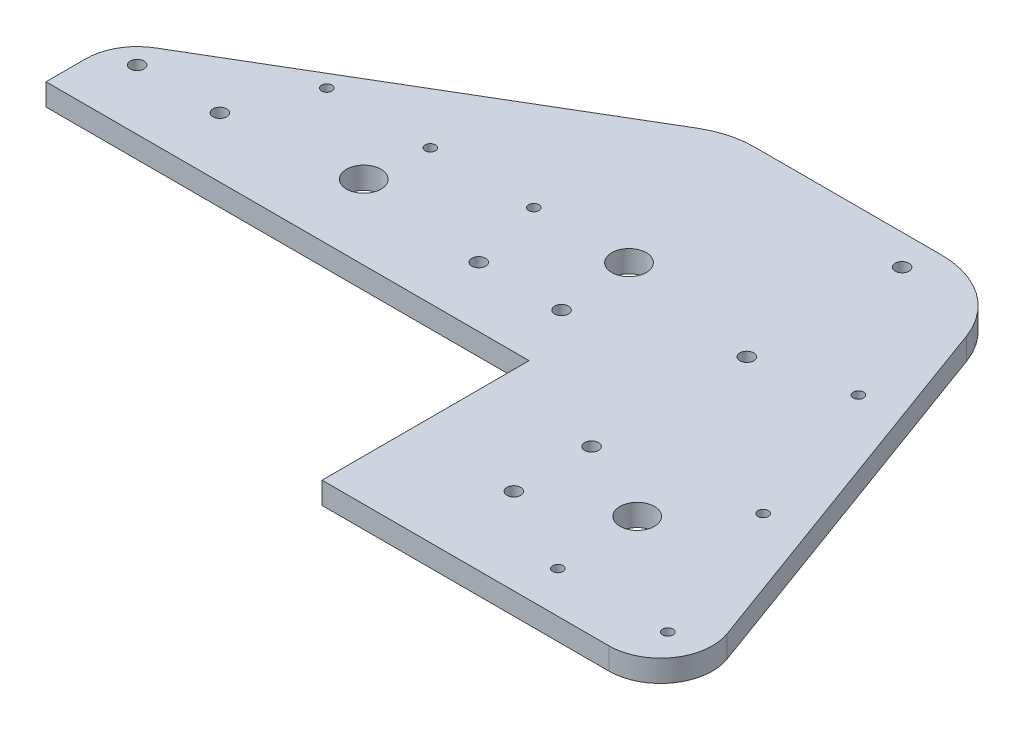
SolidWorks part; units mm, degrees
material "6063-T5"
ref_plane "Front" through (0, 0, 0) normal (0, 0, 1) x (1, 0, 0)
ref_plane "Top" through (0, 0, 0) normal (0, 1, 0) x (1, 0, 0)
ref_plane "Right" through (0, 0, 0) normal (1, 0, 0) x (0, 0, -1)
sketch "Sketch1" plane through (0, 0, 0) normal (0, 1, 0) x (1, 0, 0)
  line L0 (145, 175) -> (180.6, 175)
  line L1 (0, 0) -> (145, 0)
  line L2 (0, 0) -> (0, 175)
  line L3 (0, 175) -> (145, 175)
  line L4 (145, 0) -> (145, 175)
  line L5 (180.6, 175) -> (180.6, 0)
  line L6 (180.6, 0) -> (145, 0)
  line L7 (145, 0) -> (145, 60)
  line L8 (145, 60) -> (140, 60)
  line L9 (140, 60) -> (140, 0)
  line L10 (140, 60) -> (0, 60)
  line L11 (180.6, 175) -> (160.6, 175)
  line L12 (0, 60) -> (0, 80)
  line L13 (160.6, 175) -> (0, 80)
  line L14 (0, 60) -> (70.5, 60)
  line L15 (70.5, 60) -> (70.5, 81.59)
  line L16 (70.5, 81.59) -> (129.875, 81.59)
  line L17 (180.6, 0) -> (244.6, 0)
  line L18 (244.6, 0) -> (180.6, 175)
  line L19 (129.875, 81.59) -> (129.875, 99.09)
  line L20 (244.6, 0) -> (194.75, 0)
  line L21 (194.75, 0) -> (194.75, 36.59)
  circle A0 centre (70.5, 81.59) radius 5
  circle A2 centre (129.875, 99.09) radius 5
  circle A3 centre (194.75, 36.59) radius 5
  dimension "D10" = 59.375
  dimension "D11" = 64
  dimension "D13" = 36.59
  dimension "D1" = 175
  dimension "D2" = 145
  dimension "D3" = 35.6
  dimension "D4" = 60
  dimension "D5" = 5
  dimension "D6" = 20
  dimension "D7" = 20
  dimension "D8" = 70.5
  dimension "D9" = 21.59
  dimension "D12" = 17.5
  dimension "D14" = 49.85
extrude "Boss-Extrude2" add sketch "Sketch1" along normal blind 6.35 contours A2 A0 L10 L8 L4 L13 L2 | L0 L13 L4 L6 L5 | L17 L18 L5 | L8 L9 L1 L4 region at (162.9473, 0, -86.5132) region at (88.7844, 0, -96.4223) region at (202.0355, 0, -58.6426) region at (142.5, 0, -30)
sketch "Sketch3" plane through (0, 6.35, 0) normal (0, 1, 0) x (1, 0, 0)
  line L0 (0, 60) -> (0, 99.0944)
  line L1 (0, 99.0944) -> (42.2796, 99.0944)
  line L2 (42.2796, 99.0944) -> (32.2796, 99.0944)
  line L3 (160.6, 175) -> (0, 80) construction
  line L4 (42.2796, 99.0944) -> (72.2796, 99.0944)
  line L5 (72.2796, 99.0944) -> (102.2796, 99.0944)
  line L6 (102.2796, 99.0944) -> (208.3598, 99.0944)
  line L7 (244.6, 0) -> (180.6, 175) construction
  line L8 (208.3598, 99.0944) -> (196.3598, 99.0944)
  line L9 (244.6, 0) -> (232.0087, 0)
  line L10 (244.6, 0) -> (140, 0) construction
  line L11 (240.2114, 12) -> (228.2114, 12)
  line L12 (228.2114, 12) -> (232.0087, 12)
  line L13 (232.0087, 12) -> (232.0087, 0)
  line L14 (196.3598, 99.0944) -> (228.2114, 12)
  line L15 (228.2114, 12) -> (212.2856, 55.5472)
  line L16 (212.2856, 55.5472) -> (196.3598, 99.0944)
  line L17 (228.2114, 12) -> (196.3598, 12)
  circle A0 centre (42.2796, 99.0944) radius 1.5
  circle A1 centre (72.2796, 99.0944) radius 1.5
  circle A2 centre (102.2796, 99.0944) radius 1.5
  circle A3 centre (196.3598, 99.0944) radius 1.5
  circle A4 centre (212.2856, 55.5472) radius 1.5
  circle A5 centre (228.2114, 12) radius 1.5
  circle A6 centre (196.3598, 12) radius 1.5
  dimension "D5" = 12
  dimension "D6" = 12
  dimension "D1" = 39.0944
  dimension "D2" = 10
  dimension "D3" = 30
  dimension "D4" = 30
  dimension "D7" = 12
extrude "Cut-Extrude1" cut sketch "Sketch3" against normal blind 6.35 contours L2 A0 L4 | L4 A0 L2 | L5 A1 L4 | L4 A1 L5 | A2 | L5 A2 L6 | L6 A3 | L6 A3 | L14 A3 L6 | L14 A4 | L14 A4 | L12 A5 L14 | L14 A5 L17 | L17 A5 L12 | A6 region at (42.2796, 6.35, -99.731) region at (228.7002, 6.35, -12.6992) region at (227.4417, 6.35, -12.5381) region at (212.8835, 6.35, -55.7659) region at (211.6877, 6.35, -55.3285) region at (196.3598, 6.35, -99.731) region at (195.871, 6.35, -98.3952) region at (102.2796, 6.35, -99.731) region at (102.2796, 6.35, -98.4578) region at (72.2796, 6.35, -99.731) region at (72.2796, 6.35, -98.4578) region at (42.2796, 6.35, -98.4578) region at (197.1294, 6.35, -98.5563) region at (228.2114, 6.35, -11.3634)
sketch "Sketch4" plane through (0, 6.35, 0) normal (0, 1, 0) x (1, 0, 0)
  line L0 (170.6, 175) -> (170.6, 137.5)
  line L1 (160.6, 175) -> (180.6, 175) construction
  line L2 (170.6, 137.5) -> (170.6, 92.5)
  line L3 (170.6, 92.5) -> (170.6, 47.5)
  line L4 (170.6, 160) -> (170.6, 25)
  circle A0 centre (170.6, 137.5) radius 2
  circle A1 centre (170.6, 92.5) radius 2
  circle A2 centre (170.6, 47.5) radius 2
  circle A3 centre (170.6, 160) radius 2
  circle A4 centre (170.6, 25) radius 2
  dimension "D4" = 15
  dimension "D1" = 37.5
  dimension "D2" = 45
  dimension "D3" = 45
  dimension "D5" = 135
extrude "Cut-Extrude2" cut sketch "Sketch4" against normal blind 10 contours L0 A3 | L0 A3 | A0 | A1 | A2 | A4 region at (171.4488, 6.35, -160) region at (169.7512, 6.35, -160)
sketch "Sketch6" plane through (0, 0, 0) normal (0, -1, 0) x (-1, 0, 0)
  line L0 (-33, 77.4) -> (-9, 77.4)
  circle A0 centre (-132, 77.4) radius 2
  circle A1 centre (-108, 77.4) radius 2
  circle A2 centre (-33, 77.4) radius 2
  circle A3 centre (-33, 77.4) radius 2
  circle A4 centre (-9, 77.4) radius 2
  dimension "D1" = 24
extrude "Cut-Extrude3" cut sketch "Sketch6" against normal blind 6.35 contours A2 | A4 | A1 | A0
sketch "Sketch7" plane through (0, 6.35, 0) normal (0, 1, 0) x (1, 0, 0)
  line L7 (170.6, 25) -> (194.75, 36.59)
  line L8 (194.75, 36.59) -> (196.3598, 12)
  line L9 (194.75, 36.59) -> (170.6, 47.5)
  line L10 (170.6, 47.5) -> (212.2856, 55.5472)
  line L11 (212.2856, 55.5472) -> (194.75, 36.59)
  line L12 (170.6, 47.5) -> (170.6, 92.5)
  line L13 (170.6, 92.5) -> (170.6, 137.5)
  line L14 (10, 74.2968) -> (10, 70)
  line L15 (10, 70) -> (150, 70)
  line L16 (150, 70) -> (150, 10)
  line L17 (150, 10) -> (230.2951, 10)
  line L18 (230.2951, 10) -> (173.6094, 165)
  line L19 (173.6094, 165) -> (163.3362, 165)
  line L20 (163.3362, 165) -> (10, 74.2968)
  line L21 (10, 74.2968) -> (10, 70)
  line L22 (10, 70) -> (150, 70)
  line L23 (150, 70) -> (150, 10)
  line L24 (150, 10) -> (230.2951, 10)
  line L25 (230.2951, 10) -> (173.6094, 165)
  line L26 (173.6094, 165) -> (163.3362, 165)
  line L27 (163.3362, 165) -> (10, 74.2968)
  line L28 (170.6, 137.5) -> (170.6, 160)
  line L29 (170.6, 92.5) -> (196.3598, 99.0944)
  line L30 (170.6, 92.5) -> (129.875, 99.09)
  line L31 (129.875, 99.09) -> (132, 77.4)
  line L32 (132, 77.4) -> (108, 77.4)
  line L33 (108, 77.4) -> (102.2796, 99.0944)
  line L34 (102.2796, 99.0944) -> (129.875, 99.09)
  line L35 (102.2796, 99.0944) -> (72.2796, 99.0944)
  line L36 (72.2796, 99.0944) -> (70.5, 81.59)
  line L37 (70.5, 81.59) -> (108, 77.4)
  line L38 (70.5, 81.59) -> (33, 77.4)
  line L39 (33, 77.4) -> (72.2796, 99.0944)
  line L40 (129.875, 99.09) -> (109.6667, 133.2527)
  line L41 (102.2796, 99.0944) -> (89.2262, 121.1615)
  line L42 (42.2796, 99.0944) -> (72.2796, 99.0944)
  line L43 (129.875, 99.09) -> (170.6, 137.5)
  line L44 (170.6, 92.5) -> (150, 70)
  line L45 (133.3056, 95.4526) -> (174.0306, 133.8626)
  line L46 (126.4444, 102.7274) -> (167.1694, 141.1374)
  line L47 (171.3987, 97.4358) -> (130.6737, 104.0258)
  line L48 (169.8013, 87.5642) -> (129.0763, 94.1542)
  line L49 (171.84, 87.6562) -> (197.5998, 94.2506)
  line L50 (169.36, 97.3438) -> (195.1198, 103.9382)
  line L51 (175.6, 47.5) -> (175.6, 92.5)
  line L52 (175.6, 92.5) -> (175.6, 137.5)
  line L53 (165.6, 47.5) -> (165.6, 92.5)
  line L54 (165.6, 92.5) -> (165.6, 137.5)
  line L55 (112.8347, 78.6748) -> (106.9371, 101.0416)
  line L56 (106.9371, 101.0416) -> (93.5296, 123.7072)
  line L57 (103.1653, 76.1252) -> (97.6221, 97.1472)
  line L58 (97.6221, 97.1472) -> (84.9227, 118.6159)
  line L59 (70.5, 76.5589) -> (33.5552, 72.4309)
  line L60 (70.5, 76.5589) -> (107.4448, 72.4309)
  line L61 (70.5, 86.6211) -> (32.4448, 82.3691)
  line L62 (70.5, 86.6211) -> (108.5552, 82.3691)
  line L63 (134.743, 100.6812) -> (136.9762, 77.8875)
  line L64 (134.743, 100.6812) -> (113.9701, 135.7984)
  line L65 (125.007, 97.4988) -> (127.0238, 76.9125)
  line L66 (125.007, 97.4988) -> (105.3632, 130.7071)
  line L67 (170.6, 47.5) -> (170.6, 25)
  line L68 (170.6, 25) -> (170.6, 10)
  line L69 (170.6, 25) -> (196.3598, 12)
  line L70 (175.6, 47.5) -> (175.6, 25)
  line L71 (175.6, 25) -> (175.6, 10)
  line L72 (172.8527, 29.4638) -> (198.6125, 16.4638)
  line L73 (165.6, 47.5) -> (165.6, 25)
  line L74 (165.6, 25) -> (165.6, 10)
  line L75 (168.3473, 20.5362) -> (194.1071, 7.5362)
  line L76 (172.7634, 20.4922) -> (197.773, 32.4948)
  line L77 (215.9561, 52.152) -> (197.773, 32.4948)
  line L78 (168.4366, 29.5078) -> (191.727, 40.6852)
  line L79 (208.6151, 58.9424) -> (191.727, 40.6852)
  line L80 (171.5477, 42.5906) -> (213.2333, 50.6378)
  line L81 (169.6523, 52.4094) -> (211.3379, 60.4566)
  line L82 (189.7607, 36.2634) -> (191.3704, 11.6734)
  line L83 (199.7393, 36.9166) -> (201.3491, 12.3266)
  line L84 (194.75, 36.59) -> (228.2114, 12)
  line L85 (191.7891, 32.5609) -> (225.2506, 7.9709)
  line L86 (197.7109, 40.6191) -> (231.1723, 16.0291)
  line L87 (170.6, 92.5) -> (212.2856, 55.5472)
  line L88 (196.3598, 99.0944) -> (170.6, 47.5)
  line L89 (167.2833, 88.7585) -> (208.9688, 51.8057)
  line L90 (173.9167, 96.2415) -> (215.6023, 59.2887)
  line L91 (191.8863, 101.3279) -> (166.1266, 49.7335)
  line L92 (200.8332, 96.8609) -> (175.0734, 45.2665)
  line L93 (166.9122, 95.8764) -> (146.3122, 73.3764)
  line L94 (174.2878, 89.1236) -> (153.6878, 66.6236)
  line L95 (35.4173, 73.0232) -> (74.6969, 94.7176)
  line L96 (30.5827, 81.7768) -> (69.8622, 103.4712)
  line L97 (72.2796, 99.0944) -> (67.0025, 108.0155)
  line L98 (76.583, 101.64) -> (71.3059, 110.5612)
  line L99 (67.9761, 96.5488) -> (62.699, 105.4699)
  line L100 (67.3052, 99.6001) -> (65.5256, 82.0957)
  line L101 (77.2539, 98.5887) -> (75.4744, 81.0843)
  line L102 (175.6, 137.5) -> (175.6, 160)
  line L103 (165.6, 137.5) -> (165.6, 160)
  line L104 (42.2796, 99.0944) -> (70.5, 81.59)
  line L105 (39.644, 94.8454) -> (67.8645, 77.341)
  line L106 (44.9151, 103.3434) -> (73.1355, 85.839)
  line L107 (9, 77.4) -> (33, 77.4)
  line L108 (9, 72.4) -> (33, 72.4)
  line L109 (9, 82.4) -> (33, 82.4)
  line L110 (102.2796, 104.0944) -> (72.2796, 104.0944)
  line L111 (102.2796, 94.0944) -> (72.2796, 94.0944)
  line L112 (132, 82.4) -> (108, 82.4)
  line L113 (132, 72.4) -> (108, 72.4)
  line L114 (102.2788, 94.0944) -> (129.8742, 94.09)
  line L115 (102.2804, 104.0944) -> (129.8758, 104.09)
  circle A0 centre (9, 77.4) radius 8
  circle A1 centre (42.2796, 99.0944) radius 7.5
  circle A2 centre (33, 77.4) radius 7.5
  circle A3 centre (72.2796, 99.0944) radius 7.5
  circle A4 centre (70.5, 81.59) radius 12.5
  circle A5 centre (102.2796, 99.0944) radius 7.5
  circle A6 centre (108, 77.4) radius 8
  circle A7 centre (132, 77.4) radius 8
  circle A8 centre (129.875, 99.09) radius 12.5
  circle A9 centre (170.6, 160) radius 8
  circle A10 centre (170.6, 137.5) radius 8
  circle A11 centre (170.6, 92.5) radius 8
  circle A12 centre (196.3598, 99.0944) radius 7.5
  circle A13 centre (170.6, 47.5) radius 8
  circle A14 centre (194.75, 36.59) radius 12.5
  circle A15 centre (170.6, 25) radius 8
  circle A16 centre (196.3598, 12) radius 7.5
  circle A17 centre (212.2856, 55.5472) radius 7.5
  circle A18 centre (228.2114, 12) radius 7.5
  circle A19 centre (150, 70) radius 5
  dimension "D1" = 15
  dimension "D2" = 16
  dimension "D3" = 15
  dimension "D4" = 25
  dimension "D5" = 15
  dimension "D6" = 15
  dimension "D7" = 25
  dimension "D8" = 16
  dimension "D9" = 16
  dimension "D10" = 16
  dimension "D11" = 16
  dimension "D12" = 16
  dimension "D13" = 15
  dimension "D14" = 16
  dimension "D15" = 16
  dimension "D16" = 25
  dimension "D17" = 15
  dimension "D18" = 15
  dimension "D19" = 15
  dimension "D20" = 10
  dimension "D21" = 5
  dimension "D22" = 5
  dimension "D23" = 5
  dimension "D24" = 5
  dimension "D25" = 5
  dimension "D26" = 5
  dimension "D27" = 5
  dimension "D28" = 5
  dimension "D29" = 5
  dimension "D30" = 5
  dimension "D31" = 5
  dimension "D32" = 5
  dimension "D33" = 5
  dimension "D34" = 5
  dimension "D35" = 5
  dimension "D36" = 5
  dimension "D37" = 5
  dimension "D38" = 5
  dimension "D39" = 5
  dimension "D40" = 5
  dimension "D41" = 5
  dimension "D42" = 5
  dimension "D43" = 5
  dimension "D44" = 5
  dimension "D45" = 5
  dimension "D46" = 5
  dimension "D47" = 5
  dimension "D48" = 5
  dimension "D49" = 5
  dimension "D50" = 5
  dimension "D51" = 5
  dimension "D52" = 5
  dimension "D53" = 5
  dimension "D54" = 5
  dimension "D55" = 5
  dimension "D56" = 5
  dimension "D57" = 5
  dimension "D58" = 5
  dimension "D59" = 5
  dimension "D60" = 5
  dimension "D61" = 5
  dimension "D62" = 5
  dimension "D63" = 5
  dimension "D64" = 5
  dimension "D65" = 5
  dimension "D66" = 5
  dimension "D67" = 5
  dimension "D68" = 5
extrude "Cut-Extrude4" [suppressed] cut sketch "Sketch7" against normal blind 10 contours A11 L54 L45 A8 L47 | A12 L25 A9 L102 A10 L52 L50 | A19 L93 L48 A8 L63 A7 L22 | A19 L23 L24 L74 A15 L73 A13 L53 L94 | A16 L75 L71 L24 | A18 L85 A14 L83 A16 L24 | A14 L76 L72 L82 | A18 L25 A17 L77 A14 L86 | A14 L9 L80 A13 L70 L78 | A14 L80 L9 | A12 L92 L90 L25 | L89 L92 L81 | L91 L89 L51 | L91 L49 L90 | A8 L66 L27 L56 A5 L34 | A8 L34 A5 L55 A6 L32 A7 L65 | A7 L32 A6 L22 | A6 L60 A4 L22 | A4 L59 A2 L22 | A5 L35 A3 L101 A4 L62 L57 | A5 L58 L27 L98 A3 L35 | A3 L99 L27 L42 L96 | A2 L96 L42 L27 A1 A0 L22 | A2 L108 A0 L22
sketch "Sketch8" plane through (0, 6.35, 0) normal (0, 1, 0) x (1, 0, 0)
  line L0 (33, 77.4) -> (70.5, 81.59)
  line L1 (33, 77.4) -> (72.2796, 99.0944)
  line L2 (72.2796, 99.0944) -> (61.9821, 90.7385)
  line L3 (39.809, 78.1608) -> (38.5395, 80.4595)
  line L4 (61.9821, 90.7385) -> (65.7376, 95.4812)
  circle A0 centre (70.5, 81.59) radius 12.5
extrude "Cut-Extrude5" [suppressed] cut sketch "Sketch8" against normal through all
fillet "Fillet2" [suppressed] radius 10 type face fillet
fillet "Fillet3" [suppressed] radius 10 type face fillet
fillet "Fillet4" [suppressed] radius 5 type face fillet
fillet "Fillet5" [suppressed] radius 5 type face fillet
fillet "Fillet6" [suppressed] radius 5 type face fillet
fillet "Fillet7" [suppressed] radius 5 type face fillet
fillet "Fillet8" [suppressed] radius 2
fillet "Fillet9" [suppressed] radius 2 type face fillet
fillet "Fillet10" [suppressed] radius 2
fillet "Fillet11" [suppressed] radius 1
fillet "Fillet12" [suppressed] radius 5
sketch "Sketch10" [suppressed] plane through (0, 6.35, 0) normal (0, 1, 0) x (1, 0, 0)
  line L0 (147.6824, 74.873) -> (143.2209, 70)
  line L1 (160.6567, 89.044) -> (146.3122, 73.3764) construction
  line L2 (135.0397, 70) -> (145, 70) construction
  line L3 (156.1085, 69.2676) -> (150, 62.0878)
  line L4 (165.6, 79.6345) -> (153.6878, 66.6236) construction
  line L5 (150, 65) -> (150, 10) construction
  line L6 (150, 62.0878) -> (143.2209, 70)
  line L7 (143.2209, 70) -> (147.6824, 74.873)
  line L8 (156.1085, 69.2676) -> (147.6824, 74.873)
extrude "Boss-Extrude3" [suppressed] add sketch "Sketch10" against normal blind 6.35 contours L3 L8 L0 L6
fillet "Fillet14" [suppressed] radius 5
fillet "Fillet15" [suppressed] radius 5
fillet "Fillet16" radius 15 4 edges at (244.6, 3.175, 0) (180.6, 3.175, -175) (0, 3.175, -80) (160.6, 3.175, -175)
sketch "Sketch11" [suppressed] plane through (0, 6.35, 0) normal (0, 1, 0) x (1, 0, 0)
  line L0 (34.2207, 70) -> (65.8179, 70) construction
  line L2 (34.2207, 70) -> (40.0227, 70)
  line L3 (59.6696, 75.3488) -> (39.1108, 73.0517) construction
  line L4 (40.6109, 73.2193) -> (33.2368, 72.3953)
  line L5 (33.2368, 72.3953) -> (34.0068, 69.6019)
  line L6 (34.0068, 69.6019) -> (40.0227, 70)
  line L7 (44.296, 73.631) -> (44.6396, 70)
  line L8 (40.0227, 70) -> (40.4954, 70)
  line L9 (44.296, 73.631) -> (40.6109, 73.2193)
  ellipse E0 centre (44.4678, 71.8155) end of major axis (51.1099, 72.4442) minor radius 1.8236
extrude "Boss-Extrude4" [suppressed] add sketch "Sketch11" against normal blind 6.35
fillet "Fillet17" [suppressed] radius 3 type face fillet
fillet "Fillet18" [suppressed] radius 3 type face fillet
fillet "Fillet20" [suppressed] radius 2
fillet "Fillet21" [suppressed] radius 2
fillet "Fillet22" [suppressed] radius 2
fillet "Fillet23" [suppressed] radius 2
fillet "Fillet24" [suppressed] radius 2
fillet "Fillet25" [suppressed] radius 2
fillet "Fillet26" [suppressed] radius 1
fillet "Fillet27" [suppressed] radius 1 type face fillet
fillet "Fillet28" [suppressed] radius 1 type face fillet
fillet "Fillet29" [suppressed] radius 1
fillet "Fillet30" [suppressed] radius 1 type face fillet
sketch "Sketch12" plane through (0, 6.35, 0) normal (0, 1, 0) x (1, 0, 0)
  line L1 (157.0674, 172.9104) -> (7.3631, 84.3555) construction
  line L2 (237.2301, 20.152) -> (184.2016, 165.152) construction
  line L3 (138.8477, 162.1329) -> (182.6585, 198.0015)
  line L4 (182.6585, 198.0015) -> (187.2331, 156.8625)
  spline S0 degree 3 poles (138.8477, 162.1329) (153.7662, 167.7317) (175.983, 172.3613) (187.2331, 156.8625) knots 0 0 0 0 1 1 1 1
  point P0 (138.8477, 162.1329)
  point P1 (156.358, 166.8263)
  point P4 (175.8668, 165.4722)
  point P5 (187.2331, 156.8625)
extrude "Cut-Extrude6" cut sketch "Sketch12" against normal blind 10
sketch "Sketch13" plane through (0, 6.35, 0) normal (0, 1, 0) x (1, 0, 0)
  line L1 (140, 0) -> (239.5386, 0)
  line L2 (140, 0) -> (140, 7)
  line L3 (140, 7) -> (239.5386, 7)
  line L4 (239.5386, 0) -> (239.5386, 7)
  line L5 (110.6126, 171.6862) -> (210.2212, 171.6862)
  line L6 (110.6126, 171.6862) -> (110.6126, 146.2862)
  line L7 (110.6126, 146.2862) -> (210.2212, 146.2862)
  line L8 (210.2212, 171.6862) -> (210.2212, 146.2862)
  spline M7 degree 3 poles (187.2331, 156.8625) (175.983, 172.3613) (153.7662, 167.7317) (138.8477, 162.1329) knots 0 0 0 0 1 1 1 1
  line M8 (138.8477, 162.1329) -> (7.3631, 84.3555)
  line M15 (237.2301, 20.152) -> (187.2331, 156.8625)
  circle M20 centre (170.6, 160) radius 2
  dimension "D1" = 7
  dimension "D2" = 25.4
extrude "Cut-Extrude8" cut sketch "Sketch13" against normal blind 10 contours L7 M8 M15 M7 M20 region at (156.7781, 6.35, -154.8593)
fillet "Fillet31" radius 25.4 2 edges at (191.101, 3.175, -146.2862) (112.0586, 3.175, -146.2862)
equation "\"r1\"=10"
equation "\"r2\"=12"
equation "\"r3\"=25"
